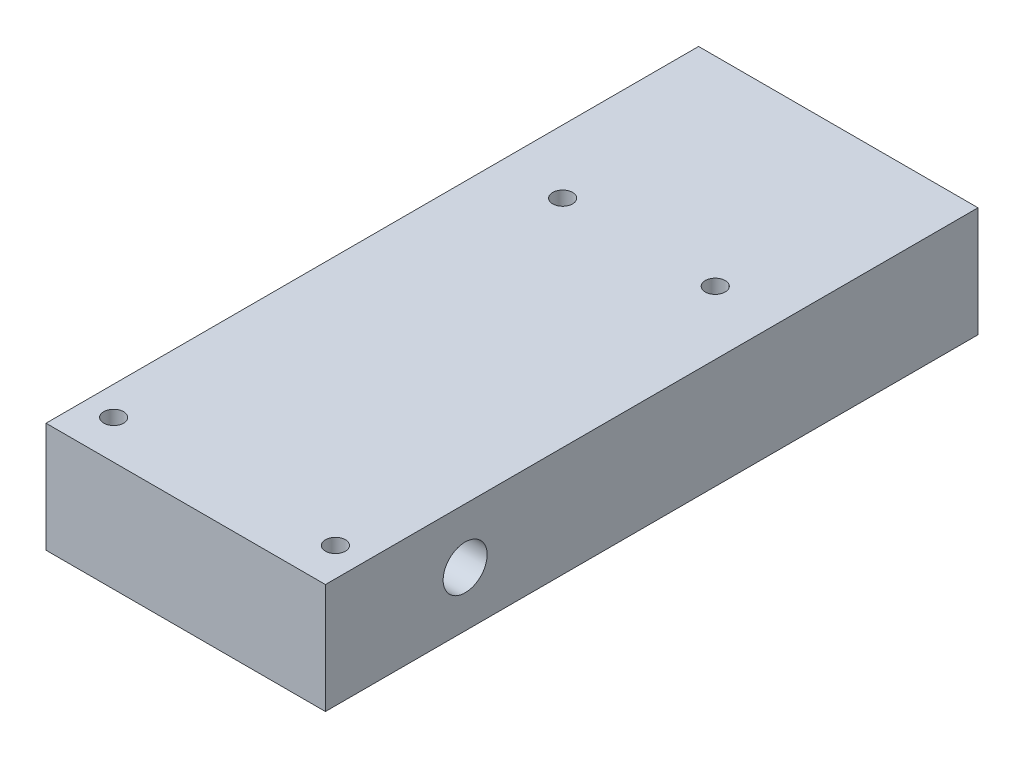
SolidWorks part; units mm, degrees
material "McMaster 6061-T6"
ref_plane "Front" through (0, 0, 0) normal (0, 0, 1) x (1, 0, 0)
ref_plane "Top" through (0, 0, 0) normal (0, 1, 0) x (1, 0, 0)
ref_plane "Right" through (0, 0, 0) normal (1, 0, 0) x (0, 0, -1)
sketch "Sketch1" plane through (0, 0, 0) normal (0, 1, 0) x (1, 0, 0)
  line L1 (-50.8, 217.4425) -> (50.8, 217.4425)
  line L2 (-50.8, 217.4425) -> (-50.8, -19.8419)
  line L3 (-50.8, -19.8419) -> (50.8, -19.8419)
  line L4 (50.8, 217.4425) -> (50.8, -19.8419)
  point P0 (0, 0)
  point P1 (0, 217.4425)
  line B0 (-57.2666, 0) -> (300.4907, 0) construction
  line B1 (58.0403, 1359.2193) -> (751.3736, 1359.2193) construction
  line B2 (0, 184.9685) -> (0, 135.7325) construction
  line B3 (-16.1045, 179.4899) -> (-16.1045, 135.5349)
  line B4 (-23.9297, -5.2923) -> (-19.0013, -5.2923)
  line B5 (-14.3059, -7.1081) -> (0, -7.7134)
  line B6 (4.4455, 217.4425) -> (-4.4455, 217.4425)
  line B7 (-10.5714, -12.7274) -> (10.5714, -12.7274)
  line B8 (14.3059, -7.1081) -> (0, -7.7134)
  line B9 (23.9297, -5.2923) -> (19.0013, -5.2923)
  line B10 (16.1045, 179.4899) -> (16.1045, 135.5349)
  arc B11 (11.5473, 186.1748) -> (-11.5473, 186.1748) centre (0, 185.2223) ccw
  arc B12 (-11.5473, 186.1748) -> (-16.1045, 179.4899) centre (-8.9229, 179.4899) ccw
  arc B13 (-16.1045, 135.5349) -> (-18.7447, 133.3526) centre (-19.0013, 136.3511) cw
  arc B14 (16.1045, 135.5349) -> (18.7447, 133.3526) centre (19.0013, 136.3511) ccw
  arc B15 (11.5473, 186.1748) -> (16.1045, 179.4899) centre (8.9229, 179.4899) cw
  circle B16 centre (-27.745, 144.9525) radius 3.6247
  circle B17 centre (-40.3206, -5.716) radius 3.6247
  circle B18 centre (40.3206, -5.716) radius 3.6247
  circle B19 centre (27.745, 144.9525) radius 3.6247
  spline B20 degree 3 poles (-18.7447, 133.3526) (-24.0724, 131.2924) (-32.603, 124.9988) (-41.6376, 111.3739) (-43.9656, 96.1245) (-45.0501, 79.5297) (-45.8816, 62.8086) (-45.6029, 47.686) (-43.2164, 25.6573) (-35.9471, 10.0985) (-28.9898, -1.1126) knots 0 0 0 0 0.114752 0.211975 0.323248 0.422595 0.550935 0.662789 0.729557 1 1 1 1
  spline B21 degree 3 poles (-28.9898, -1.1126) (-27.9742, -3.0999) (-26.1032, -4.7308) (-23.9297, -5.2923) knots 0 0 0 0 1 1 1 1
  spline B22 degree 3 poles (-19.0013, -5.2923) (-16.9934, -4.8476) (-16.0767, -6.8562) (-14.3059, -7.1081) knots 0 0 0 0 1 1 1 1
  spline B23 degree 3 poles (-4.4455, 217.4425) (-6.5665, 217.6433) (-8.2866, 214.6032) (-8.8185, 209.8097) (-10.4503, 205.542) (-13.9883, 202.8783) (-17.1351, 200.8787) (-21.9225, 195.1985) (-25.1053, 187.0236) (-30.5496, 174.0979) (-35.9601, 157.7735) (-44.7383, 128.666) (-52.5309, 73.6432) (-50.0644, 26.1167) (-49.0771, -5.2923) knots 0 0 0 0 0.022097 0.039559 0.063259 0.077264 0.095563 0.110967 0.171488 0.206517 0.29131 0.391743 0.596457 1 1 1 1
  spline B24 degree 3 poles (-49.0771, -5.2923) (-50.5689, -10.9401) (-38.8329, -13.5043) (-37.4191, -14.3419) knots 0 0 0 0 1 1 1 1
  spline B25 degree 1 poles (-37.4191, -14.3419) (-18.3852, -19.4149) knots 0 0 1 1
  spline B26 degree 3 poles (-18.3852, -19.4149) (-11.6134, -21.8049) (-15.7198, -13.4118) (-10.5714, -12.7274) knots 0 0 0 0 1 1 1 1
  spline B27 degree 3 poles (18.3852, -19.4149) (11.6134, -21.8049) (15.7198, -13.4118) (10.5714, -12.7274) knots 0 0 0 0 1 1 1 1
  spline B28 degree 1 poles (37.4191, -14.3419) (18.3852, -19.4149) knots 0 0 1 1
  spline B29 degree 3 poles (49.0771, -5.2923) (50.5689, -10.9401) (38.8329, -13.5043) (37.4191, -14.3419) knots 0 0 0 0 1 1 1 1
  spline B30 degree 3 poles (4.4455, 217.4425) (6.5665, 217.6433) (8.2866, 214.6032) (8.8185, 209.8097) (10.4503, 205.542) (13.9883, 202.8783) (17.1351, 200.8787) (21.9225, 195.1985) (25.1053, 187.0236) (30.5496, 174.0979) (35.9601, 157.7735) (44.7383, 128.666) (52.5309, 73.6432) (50.0644, 26.1167) (49.0771, -5.2923) knots 0 0 0 0 0.022097 0.039559 0.063259 0.077264 0.095563 0.110967 0.171488 0.206517 0.29131 0.391743 0.596457 1 1 1 1
  spline B31 degree 3 poles (19.0013, -5.2923) (16.9934, -4.8476) (16.0767, -6.8562) (14.3059, -7.1081) knots 0 0 0 0 1 1 1 1
  spline B32 degree 3 poles (28.9898, -1.1126) (27.9742, -3.0999) (26.1032, -4.7308) (23.9297, -5.2923) knots 0 0 0 0 1 1 1 1
  spline B33 degree 3 poles (18.7447, 133.3526) (24.0724, 131.2924) (32.603, 124.9988) (41.6376, 111.3739) (43.9656, 96.1245) (45.0501, 79.5297) (45.8816, 62.8086) (45.6029, 47.686) (43.2164, 25.6573) (35.9471, 10.0985) (28.9898, -1.1126) knots 0 0 0 0 0.114752 0.211975 0.323248 0.422595 0.550935 0.662789 0.729557 1 1 1 1
  dimension "D1" = 101.6
  dimension "D2" = 237.2844
sketch_block_instance "Block-RoughDrillPressMounting-1"
sketch_block "Block-RoughDrillPressMounting"
extrude "Boss-Extrude1" add sketch "Sketch1" against normal blind 39.9999 contours B26 B25 B24 B23 L1 L2 L3 | L1 B30 B29 B28 B27 L3 L4 | B30 L1 B23 B24 B25 B26 B7 B27 B28 B29 B18 B17 B16 B19 B14 B33 B32 B9 B31 B8 B5 B22 B4 B21 B20 B13 B3 B12 B11 B15 B10 | B33 B14 B10 B15 B11 B12 B3 B13 B20 B21 B4 B22 B5 B8 B31 B9 B32 | L3 B27 B7 B26 region at (0, 0, -214.8633) region at (-38.3174, 0, -161.5358) region at (38.3167, 0, -161.5392) region at (0, 0, 16.4213) region at (0, 0, -77.7954)
sketch "Sketch2" plane through (-50.8, 0, 0) normal (-1, 0, 0) x (0, 0, 1)
  line L1 (-217.4425, 0) -> (19.8419, 0) construction
  line L2 (19.8419, -39.9999) -> (19.8419, 0) construction
  circle A0 centre (-30.9581, -20) radius 8
  line B0 (-17.6916, 0) -> (-44.2246, 0)
  line B1 (-44.2246, -40) -> (-17.6916, -40)
  arc B2 (-44.2246, 0) -> (-44.2246, -40) centre (-30.9581, -20) ccw
  arc B3 (-17.6916, -40) -> (-17.6916, 0) centre (-30.9581, -20) ccw
  arc B4 (-30.9581, -6) -> (-30.9581, -34) centre (-30.9581, -20) ccw
  arc B5 (-30.9581, -34) -> (-30.9581, -6) centre (-30.9581, -20) ccw
  arc B6 (-17.5231, -36.185) -> (-17.5231, -30.685) centre (-17.5231, -33.435) ccw
  arc B7 (-17.5231, -30.685) -> (-17.5231, -36.185) centre (-17.5231, -33.435) ccw
  arc B8 (-11.9581, -22.75) -> (-11.9581, -17.25) centre (-11.9581, -20) ccw
  arc B9 (-11.9581, -17.25) -> (-11.9581, -22.75) centre (-11.9581, -20) ccw
  arc B10 (-17.5231, -9.315) -> (-17.5231, -3.815) centre (-17.5231, -6.565) ccw
  arc B11 (-17.5231, -3.815) -> (-17.5231, -9.315) centre (-17.5231, -6.565) ccw
  arc B12 (-44.3932, -36.185) -> (-44.3932, -30.685) centre (-44.3932, -33.435) ccw
  arc B13 (-44.3932, -30.685) -> (-44.3932, -36.185) centre (-44.3932, -33.435) ccw
  arc B14 (-49.9581, -22.75) -> (-49.9581, -17.25) centre (-49.9581, -20) ccw
  arc B15 (-49.9581, -17.25) -> (-49.9581, -22.75) centre (-49.9581, -20) ccw
  arc B16 (-44.3932, -9.315) -> (-44.3932, -3.815) centre (-44.3932, -6.565) ccw
  arc B17 (-44.3932, -3.815) -> (-44.3932, -9.315) centre (-44.3932, -6.565) ccw
  dimension "D2" = 16
  dimension "D1" = 50.8
sketch_block_instance "Block-Screw Nut Mount-1"
sketch_block "Block-Screw Nut Mount"
extrude "Cut-Extrude1" cut sketch "Sketch2" against normal blind 12.7 contours B16 B17 | B14 B15 | B12 B13 | B6 B7 | B8 B9 | B10 B11 region at (-50.8, -33.435, -17.5231) region at (-50.8, -20, -11.9581) region at (-50.8, -6.565, -17.5231) region at (-50.8, -33.435, -44.3932) region at (-50.8, -20, -49.9581) region at (-50.8, -6.565, -44.3932)
extrude "Cut-Extrude2" cut sketch "Sketch2<5>" against normal blind 32 contours B4 B5 | A0 region at (-50.8, -20, -30.9581) region at (-50.8, -20, -17.3541)
sketch "Sketch2<5>" plane through (-50.8, 0, 0) normal (-1, 0, 0) x (0, 0, 1) same geometry as "Sketch2"
extrude "Cut-Extrude3" cut sketch "Sketch2<6>" against normal through all contours A0 region at (-50.8, -20, -30.9581)
sketch "Sketch2<6>" plane through (-50.8, 0, 0) normal (-1, 0, 0) x (0, 0, 1) same geometry as "Sketch2"
sketch "Sketch3" plane through (0, -39.9999, 0) normal (0, -1, 0) x (1, 0, 0)
  line L0 (-50.8, -217.4425) -> (-50.8, 19.8419) construction
  point P2 (-50.8, -30.9581)
  point P13 (-50.8, -30.9581)
  line B0 (-50.8, -17.6916) -> (-50.8, -44.2246)
  arc B1 (-18.219, -12.5581) -> (-18.219, -8.3581) centre (-18.219, -10.4581) ccw
  arc B2 (-18.219, -8.3581) -> (-18.219, -12.5581) centre (-18.219, -10.4581) ccw
  arc B3 (-44.219, -12.5581) -> (-44.219, -8.3581) centre (-44.219, -10.4581) ccw
  arc B4 (-44.219, -8.3581) -> (-44.219, -12.5581) centre (-44.219, -10.4581) ccw
  arc B5 (-18.219, -53.5581) -> (-18.219, -49.3581) centre (-18.219, -51.4581) ccw
  arc B6 (-18.219, -49.3581) -> (-18.219, -53.5581) centre (-18.219, -51.4581) ccw
  arc B7 (-44.219, -53.5581) -> (-44.219, -49.3581) centre (-44.219, -51.4581) ccw
  arc B8 (-44.219, -49.3581) -> (-44.219, -53.5581) centre (-44.219, -51.4581) ccw
sketch_block_instance "Block-Carriage Mount-1"
sketch_block "Block-Carriage Mount"
extrude "Cut-Extrude4" cut sketch "Sketch3" against normal blind 6.35 contours B7 B8 | B5 B6 | B1 B2 | B3 B4 region at (-18.219, -39.9999, -10.4581) region at (-44.219, -39.9999, -10.4581) region at (-18.219, -39.9999, -51.4581) region at (-44.219, -39.9999, -51.4581)
